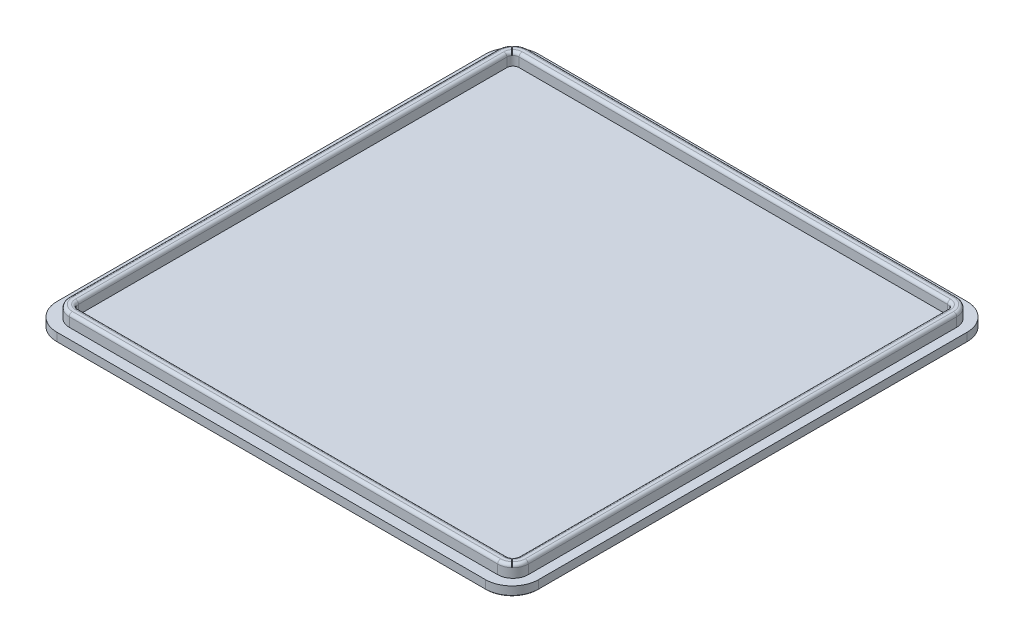
SolidWorks part; units mm, degrees
ref_plane "Front Plane" through (0, 0, 0) normal (0, 0, 1) x (1, 0, 0)
ref_plane "Top Plane" through (0, 0, 0) normal (0, 1, 0) x (1, 0, 0)
ref_plane "Right Plane" through (0, 0, 0) normal (1, 0, 0) x (0, 0, -1)
sketch "Sketch1" plane through (0, 0, 0) normal (0, 1, 0) x (1, 0, 0)
  line L8 (-70, -78.7) -> (70, -78.7)
  line L9 (78.7, -70) -> (78.7, 70)
  line L10 (70, 78.7) -> (-70, 78.7)
  line L11 (-78.7, 70) -> (-78.7, -70)
  line L12 (-70, 70) -> (70, -70) construction
  line L13 (70, -70) -> (70, 70) construction
  line L14 (70, 70) -> (-70, -70) construction
  arc A8 (-78.7, -70) -> (-70, -78.7) centre (-70, -70) ccw
  arc A9 (70, -78.7) -> (78.7, -70) centre (70, -70) ccw
  arc A10 (78.7, 70) -> (70, 78.7) centre (70, 70) ccw
  arc A11 (-70, 78.7) -> (-78.7, 70) centre (-70, 70) ccw
  point P13 (0, 0)
  dimension "D1" = 140
  dimension "D2" = 140
extrude "Boss-Extrude1" add sketch "Sketch1" along normal blind 3
sketch "Sketch2" plane through (0, 3, 0) normal (0, 1, 0) x (1, 0, 0)
  line L0 (-74.3691, 69.6926) -> (-74.3691, -70.3074)
  line L9 (-69.3691, -75.3074) -> (70.6309, -75.3074)
  line L12 (75.6309, -70.3074) -> (75.6309, 69.6926)
  line L15 (70.6309, 74.6926) -> (-69.3691, 74.6926)
  arc A11 (-74.3691, -70.3074) -> (-69.3691, -75.3074) centre (-69.3691, -70.3074) ccw
  arc A12 (75.6309, -70.3074) -> (70.6309, -75.3074) centre (70.6309, -70.3074) cw
  arc A13 (75.6309, 69.6926) -> (70.6309, 74.6926) centre (70.6309, 69.6926) ccw
  arc A14 (-74.3691, 69.6926) -> (-69.3691, 74.6926) centre (-69.3691, 69.6926) cw
  point P0 (0, 0)
  dimension "D1" = 5
extrude "Extrude-Thin1" add sketch "Sketch2" along normal blind 4 thin thin type one direction reverse wall 3
fillet "Fillet1" radius 1 16 edges at (-71.3691, 7, 0.3074) (0.6309, 7, 72.3074) (72.6309, 7, 0.3074) (0.6309, 7, -71.6926) (0.6309, 7, -74.6926) (75.6309, 7, 0.3074) (0.6309, 7, 75.3074) (-74.3691, 7, 0.3074) (72.0451, 7, 71.7216) (72.0451, 7, -71.1068) (-70.7833, 7, -71.1068) (-70.7833, 7, 71.7216) (-72.9046, 7, -73.2282) (74.1665, 7, -73.2282) (74.1665, 7, 73.8429) (-72.9046, 7, 73.8429)
sketch "Sketch3" plane through (0, 7, 0) normal (0, 1, 0) x (1, 0, 0)
  line L0 (-75, 70) -> (-75, 75) construction
  line L1 (-70, 75) -> (-75, 75) construction
  line L2 (-75.0707, 74.9293) -> (-74.9293, 75.0707) construction
  line L3 (-75.0707, 74.9293) -> (78.5176, -78.659)
  line L4 (78.5176, -78.659) -> (78.659, -78.5176)
  line L5 (78.659, -78.5176) -> (-74.9293, 75.0707)
  line L6 (-74.9293, 75.0707) -> (-75.0707, 74.9293)
  point P10 (-75, 75)
extrude "Cut-Extrude1" cut sketch "Sketch3" against normal blind 3.8 draft 2.5
chamfer "Chamfer1" distance 0.3 angle 45 8 edges at (0, 0, 78.7) (76.1518, 0, 76.1518) (78.7, 0, 0) (76.1518, 0, -76.1518) (0, 0, -78.7) (-76.1518, 0, -76.1518) (-78.7, 0, 0) (-76.1518, 0, 76.1518)
